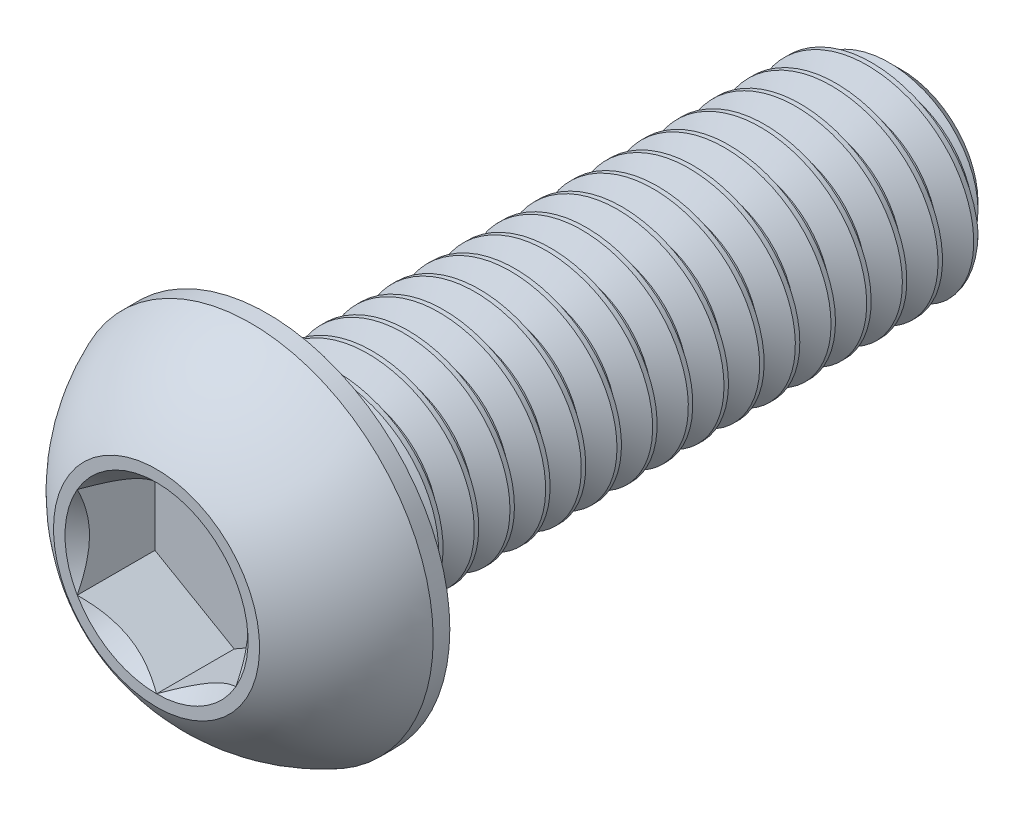
SolidWorks part; units mm, degrees
ref_plane "Front" through (0, 0, 0) normal (0, 0, 1) x (1, 0, 0)
ref_plane "Top" through (0, 0, 0) normal (0, 1, 0) x (1, 0, 0)
ref_plane "Right" through (0, 0, 0) normal (1, 0, 0) x (0, 0, -1)
sketch "Sketch1" plane through (0, 0, 0) normal (1, 0, 0) x (0, 0, -1)
  line L2 (1.4, 1.3) -> (9.4, 1.3)
  line L3 (9.4, 1.3) -> (9.4, 0)
  line L4 (9.4, 0) -> (1.4, 0)
  line L6 (1.19, 2.3) -> (1.4, 2.3) construction
  line L7 (9.4, 1.3) -> (9.4, -1.3) construction
  line L8 (0, 0) -> (1.4, 0) construction
  line L9 (1.4, 2.3) -> (1.4, -2.3) construction
  line L11 (1.4, 1.3) -> (1.4, 0)
  line L13 (0, 1) -> (0, -1) construction
  line L14 (0, 1) -> (0, 1.3) construction
  line L15 (9.3719, 1.3487) -> (9.5969, 0.959) construction
  line L16 (9.5969, 0.959) -> (9.8219, 1.3487) construction
  line L17 (9.8219, 1.3487) -> (9.3719, 1.3487) construction
  line L18 (9.4, 1.3) -> (9.7938, 1.3) construction
  line L19 (9.5969, 1.3487) -> (9.5969, 1.3) construction
  line L20 (9.5969, 1.3) -> (9.5969, 1.0077) construction
  line L21 (9.5969, 1.0077) -> (9.5969, 0.959) construction
  line L22 (9.5688, 1.0077) -> (9.625, 1.0077)
  line L23 (9.3859, 1.3244) -> (9.8078, 1.3244)
  line L24 (9.625, 1.0077) -> (9.8078, 1.3244)
  line L25 (9.5688, 1.0077) -> (9.3859, 1.3244)
  line L26 (9.0625, 1.3) -> (9.4, 0.9625)
  arc A3 (0, 1.3) -> (1.19, 2.3) centre (2.1076, 0) cw construction
  point P29 (9.5969, 1.3244)
  point P30 (8.275, -1.3)
  dimension "D1" = 0.21
  dimension "Pitch" = 0.45
  dimension "D3" = 0.0563
  dimension "D2" = 0.3375
  dimension "D4" = 45
  dimension "D5" = 1.125
sketch "Sketch10" plane through (0, 0, 0) normal (1, 0, 0) x (0, 0, -1)
  line L0 (9.0625, 1.3) -> (9.4, 0.9625) construction
  line L1 (9.0625, 1.3) -> (9.4, 0.9625)
  line L4 (9.4, 1.3) -> (1.4, 1.3)
  line L5 (9.4, 0) -> (9.4, 1.3)
  line L6 (1.4, 0) -> (9.4, 0)
  line L7 (1.4, 1.3) -> (1.4, 0)
  line L8 (9.0625, 1.3) -> (1.4, 1.3)
  line L9 (9.4, 0) -> (9.4, 0.9625)
  line L10 (1.4, 0) -> (9.4, 0)
  line L11 (1.4, 1.3) -> (1.4, 0)
  dimension "D1" = 0
revolve "Revolve3" add sketch "Sketch10" angle 360 about L8
sketch "Sketch7" plane through (0, 0, 0) normal (1, 0, 0) x (0, 0, -1)
  line L6 (1.19, 2.3) -> (1.4, 2.3) construction
  line L8 (0, 0) -> (1.4, 0) construction
  line L11 (1.4, 2.3) -> (1.4, -2.3) construction
  line L12 (1.19, 2.3) -> (1.4, 2.3)
  line L13 (0, 0) -> (1.4, 0)
  line L14 (0, 1) -> (0, -1) construction
  line L15 (1.4, 2.3) -> (1.4, 0)
  line L16 (0, 1.3) -> (0, 0)
  arc A2 (1.19, 2.3) -> (0, 1.3) centre (2.1076, 0) ccw construction
  arc A3 (1.19, 2.3) -> (0, 1.3) centre (2.1076, 0) ccw
revolve "Revolve2" add sketch "Sketch7" angle 360 mid plane about L13
sketch "Sketch5" plane through (0, 0, 0) normal (0, 0, 1) x (1, 0, 0)
  line L1 (1, -0.5774) -> (1, 0.5774)
  line L2 (1, 0.5774) -> (0, 1.1547)
  line L3 (0, 1.1547) -> (-1, 0.5774)
  line L4 (-1, 0.5774) -> (-1, -0.5774)
  line L5 (-1, -0.5774) -> (0, -1.1547)
  line L6 (0, -1.1547) -> (1, -0.5774)
  circle A0 centre (0, 0) radius 1 construction
extrude "Cut-Extrude2" cut sketch "Sketch5" against normal blind 0.98
sketch "Sketch6" plane through (0, 0, 0) normal (0, 0, 1) x (1, 0, 0)
  circle A0 centre (0, 0) radius 1.1547
extrude "Cut-Extrude3" cut sketch "Sketch6" against normal blind 0.98 draft 45
sketch "Sketch9" plane through (0, 0, -1.4) normal (0, 0, -1) x (-1, 0, 0)
  circle A0 centre (0, 0) radius 1.3 construction
  circle A4 centre (0, 0) radius 1.3
split "Split1" bodies to split 113 resulting bodies 123 124 split by face at (2.3, 0, -1.4)
sketch "Sketch11" plane through (0, 0, -9.4) normal (0, 0, -1) x (-1, 0, 0)
  circle A0 centre (0, 0) radius 1.3 construction
  circle A1 centre (0, 0) radius 1.3
curve "Helix/Spiral1" pitch 0.45 height 9.4 radius 1.3 centre (0, 0, -9.4) axis (0, 0, 1) start towards (0, 1, 0)
sketch "Sketch12" plane through (0, 0, 0) normal (1, 0, 0) x (0, 0, -1)
  line L0 (9.5688, 1.0077) -> (9.625, 1.0077) construction
  line L1 (9.625, 1.0077) -> (9.8078, 1.3244) construction
  line L2 (9.3859, 1.3244) -> (9.8078, 1.3244) construction
  line L3 (9.5688, 1.0077) -> (9.3859, 1.3244) construction
  line L4 (9.5688, 1.0077) -> (9.625, 1.0077)
  line L5 (9.625, 1.0077) -> (9.8078, 1.3244)
  line L6 (9.3859, 1.3244) -> (9.8078, 1.3244)
  line L7 (9.5688, 1.0077) -> (9.3859, 1.3244)
sweep "Cut-Sweep2" cut profiles "Sketch12" path "Helix/Spiral1" align with end faces yes
extrude "Boss-Extrude1" add sketch "Sketch9" along normal blind 10 draft 45
equation "\"D1@Cut-Extrude2\" = \"Head Ht@Sketch1\" * .7"
equation "\"D1@Sketch1\" = \"Head Ht@Sketch1\" * .15"
equation "\"D1@Cut-Extrude3\" = \"D1@Cut-Extrude2\""
equation "\"D3@Sketch1\" = \"Pitch@Sketch1\" / 8"
equation "\"D2@Sketch1\"=\"Pitch@Sketch1\"*0.75"
equation "\"D3@Helix/Spiral1\" = \"Lg@Sketch1\" + \"Head Ht@Sketch1\""
equation "\"D4@Helix/Spiral1\"=\"pitch@sketch1\""
equation "\"D5@Sketch1\"=\"Pitch@Sketch1\"*2.5"
